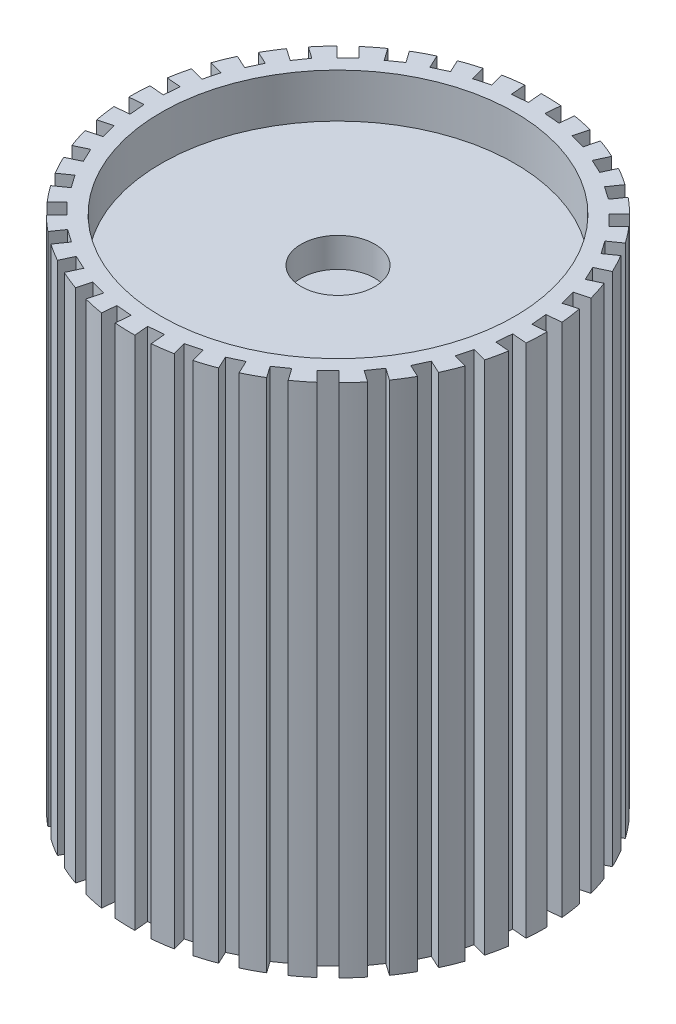
SolidWorks part; units mm, degrees
ref_plane "Front Plane" through (0, 0, 0) normal (0, 0, 1) x (1, 0, 0)
ref_plane "Top Plane" through (0, 0, 0) normal (0, 1, 0) x (1, 0, 0)
ref_plane "Right Plane" through (0, 0, 0) normal (1, 0, 0) x (0, 0, -1)
other "Configuration Table"
sketch "草图1" plane through (0, 0, 0) normal (0, 1, 0) x (1, 0, 0)
  circle A0 centre (0, 0) radius 13
  dimension "D1" = 26
extrude "凸台-拉伸1" add sketch "草图1" along normal blind 35
sketch "草图6" plane through (0, 35, 0) normal (0, 1, 0) x (1, 0, 0)
  circle A0 centre (0, 0) radius 14
  dimension "D1" = 28
extrude "凸台-拉伸4" add sketch "草图6" against normal through all
sketch "草图2" plane through (0, 35, 0) normal (0, 1, 0) x (1, 0, 0)
  circle A0 centre (0, 0) radius 12
  dimension "D1" = 24
extrude "切除-拉伸1" cut sketch "草图2" against normal blind 3
sketch "草图7" plane through (0, 35, 0) normal (0, 1, 0) x (1, 0, 0)
  line L0 (-15.6468, 4.1422) -> (-12.5671, 3.3269)
  line L1 (-15.6468, 4.1422) -> (-15.3762, 5.1646)
  line L2 (-12.5671, 3.3269) -> (-12.2964, 4.3493)
  line L3 (-15.3762, 5.1646) -> (-12.2964, 4.3493)
  line L4 (-14.6898, 6.7963) -> (-11.7985, 5.4586)
  line L5 (-14.6898, 6.7963) -> (-14.2457, 7.7562)
  line L6 (-14.2457, 7.7562) -> (-11.3544, 6.4185)
  line L7 (-11.7985, 5.4586) -> (-11.3544, 6.4185)
  line L8 (-13.2865, 9.2439) -> (-10.6713, 7.4245)
  line L9 (-13.2865, 9.2439) -> (-12.6825, 10.1121)
  line L10 (-12.6825, 10.1121) -> (-10.0673, 8.2926)
  line L11 (-10.6713, 7.4245) -> (-10.0673, 8.2926)
  line L12 (-11.4794, 11.4107) -> (-9.22, 9.1647)
  line L13 (-11.4794, 11.4107) -> (-10.7338, 12.1608)
  line L14 (-10.7338, 12.1608) -> (-8.4744, 9.9148)
  line L15 (-9.22, 9.1647) -> (-8.4744, 9.9148)
  line L16 (-9.3236, 13.2307) -> (-7.4884, 10.6265)
  line L17 (-9.3236, 13.2307) -> (-8.4591, 13.8399)
  line L18 (-8.4591, 13.8399) -> (-6.6239, 11.2358)
  line L19 (-7.4884, 10.6265) -> (-6.6239, 11.2358)
  line L20 (-6.8845, 14.6487) -> (-5.5294, 11.7654)
  line L21 (-6.8845, 14.6487) -> (-5.9273, 15.0986)
  line L22 (-5.9273, 15.0986) -> (-4.5722, 12.2153)
  line L23 (-5.5294, 11.7654) -> (-4.5722, 12.2153)
  line L24 (-4.2361, 15.6217) -> (-3.4024, 12.5469)
  line L25 (-4.2361, 15.6217) -> (-3.2154, 15.8985)
  line L26 (-3.2154, 15.8985) -> (-2.3816, 12.8237)
  line L27 (-3.4024, 12.5469) -> (-2.3816, 12.8237)
  line L28 (-1.4591, 16.1199) -> (-1.1719, 12.9471)
  line L29 (-1.4591, 16.1199) -> (-0.4058, 16.2153)
  line L30 (-0.4058, 16.2153) -> (-0.1186, 13.0424)
  line L31 (-1.1719, 12.9471) -> (-0.1186, 13.0424)
  line L32 (1.3622, 16.1284) -> (1.0941, 12.9539)
  line L33 (1.3622, 16.1284) -> (2.4161, 16.0394)
  line L34 (2.4161, 16.0394) -> (2.148, 12.8649)
  line L35 (1.0941, 12.9539) -> (2.148, 12.8649)
  line L36 (4.1422, 15.6468) -> (3.3269, 12.5671)
  line L37 (4.1422, 15.6468) -> (5.1646, 15.3762)
  line L38 (5.1646, 15.3762) -> (4.3493, 12.2964)
  line L39 (3.3269, 12.5671) -> (4.3493, 12.2964)
  line L40 (6.7963, 14.6898) -> (5.4586, 11.7985)
  line L41 (6.7963, 14.6898) -> (7.7562, 14.2457)
  line L42 (7.7562, 14.2457) -> (6.4185, 11.3544)
  line L43 (5.4586, 11.7985) -> (6.4185, 11.3544)
  line L44 (9.2439, 13.2865) -> (7.4245, 10.6713)
  line L45 (9.2439, 13.2865) -> (10.1121, 12.6825)
  line L46 (10.1121, 12.6825) -> (8.2926, 10.0673)
  line L47 (7.4245, 10.6713) -> (8.2926, 10.0673)
  line L48 (11.4107, 11.4794) -> (9.1647, 9.22)
  line L49 (11.4107, 11.4794) -> (12.1608, 10.7338)
  line L50 (12.1608, 10.7338) -> (9.9148, 8.4744)
  line L51 (9.1647, 9.22) -> (9.9148, 8.4744)
  line L52 (13.2307, 9.3236) -> (10.6265, 7.4884)
  line L53 (13.2307, 9.3236) -> (13.8399, 8.4591)
  line L54 (13.8399, 8.4591) -> (11.2358, 6.6239)
  line L55 (10.6265, 7.4884) -> (11.2358, 6.6239)
  line L56 (14.6487, 6.8845) -> (11.7654, 5.5294)
  line L57 (14.6487, 6.8845) -> (15.0986, 5.9273)
  line L58 (15.0986, 5.9273) -> (12.2153, 4.5722)
  line L59 (11.7654, 5.5294) -> (12.2153, 4.5722)
  line L60 (15.6217, 4.2361) -> (12.5469, 3.4024)
  line L61 (15.6217, 4.2361) -> (15.8985, 3.2154)
  line L62 (15.8985, 3.2154) -> (12.8237, 2.3816)
  line L63 (12.5469, 3.4024) -> (12.8237, 2.3816)
  line L64 (16.1199, 1.4591) -> (12.9471, 1.1719)
  line L65 (16.1199, 1.4591) -> (16.2153, 0.4058)
  line L66 (16.2153, 0.4058) -> (13.0424, 0.1186)
  line L67 (12.9471, 1.1719) -> (13.0424, 0.1186)
  line L68 (16.1284, -1.3622) -> (12.9539, -1.0941)
  line L69 (16.1284, -1.3622) -> (16.0394, -2.4161)
  line L70 (16.0394, -2.4161) -> (12.8649, -2.148)
  line L71 (12.9539, -1.0941) -> (12.8649, -2.148)
  line L72 (15.6468, -4.1422) -> (12.5671, -3.3269)
  line L73 (15.6468, -4.1422) -> (15.3762, -5.1646)
  line L74 (15.3762, -5.1646) -> (12.2964, -4.3493)
  line L75 (12.5671, -3.3269) -> (12.2964, -4.3493)
  line L76 (14.6898, -6.7963) -> (11.7985, -5.4586)
  line L77 (14.6898, -6.7963) -> (14.2457, -7.7562)
  line L78 (14.2457, -7.7562) -> (11.3544, -6.4185)
  line L79 (11.7985, -5.4586) -> (11.3544, -6.4185)
  line L80 (13.2865, -9.2439) -> (10.6713, -7.4245)
  line L81 (13.2865, -9.2439) -> (12.6825, -10.1121)
  line L82 (12.6825, -10.1121) -> (10.0673, -8.2926)
  line L83 (10.6713, -7.4245) -> (10.0673, -8.2926)
  line L84 (11.4794, -11.4107) -> (9.22, -9.1647)
  line L85 (11.4794, -11.4107) -> (10.7338, -12.1608)
  line L86 (10.7338, -12.1608) -> (8.4744, -9.9148)
  line L87 (9.22, -9.1647) -> (8.4744, -9.9148)
  line L88 (9.3236, -13.2307) -> (7.4884, -10.6265)
  line L89 (9.3236, -13.2307) -> (8.4591, -13.8399)
  line L90 (8.4591, -13.8399) -> (6.6239, -11.2358)
  line L91 (7.4884, -10.6265) -> (6.6239, -11.2358)
  line L92 (6.8845, -14.6487) -> (5.5294, -11.7654)
  line L93 (6.8845, -14.6487) -> (5.9273, -15.0986)
  line L94 (5.9273, -15.0986) -> (4.5722, -12.2153)
  line L95 (5.5294, -11.7654) -> (4.5722, -12.2153)
  line L96 (4.2361, -15.6217) -> (3.4024, -12.5469)
  line L97 (4.2361, -15.6217) -> (3.2154, -15.8985)
  line L98 (3.2154, -15.8985) -> (2.3816, -12.8237)
  line L99 (3.4024, -12.5469) -> (2.3816, -12.8237)
  line L100 (1.4591, -16.1199) -> (1.1719, -12.9471)
  line L101 (1.4591, -16.1199) -> (0.4058, -16.2153)
  line L102 (0.4058, -16.2153) -> (0.1186, -13.0424)
  line L103 (1.1719, -12.9471) -> (0.1186, -13.0424)
  line L104 (-1.3622, -16.1284) -> (-1.0941, -12.9539)
  line L105 (-1.3622, -16.1284) -> (-2.4161, -16.0394)
  line L106 (-2.4161, -16.0394) -> (-2.148, -12.8649)
  line L107 (-1.0941, -12.9539) -> (-2.148, -12.8649)
  line L108 (-4.1422, -15.6468) -> (-3.3269, -12.5671)
  line L109 (-4.1422, -15.6468) -> (-5.1646, -15.3762)
  line L110 (-5.1646, -15.3762) -> (-4.3493, -12.2964)
  line L111 (-3.3269, -12.5671) -> (-4.3493, -12.2964)
  line L112 (-6.7963, -14.6898) -> (-5.4586, -11.7985)
  line L113 (-6.7963, -14.6898) -> (-7.7562, -14.2457)
  line L114 (-7.7562, -14.2457) -> (-6.4185, -11.3544)
  line L115 (-5.4586, -11.7985) -> (-6.4185, -11.3544)
  line L116 (-9.2439, -13.2865) -> (-7.4245, -10.6713)
  line L117 (-9.2439, -13.2865) -> (-10.1121, -12.6825)
  line L118 (-10.1121, -12.6825) -> (-8.2926, -10.0673)
  line L119 (-7.4245, -10.6713) -> (-8.2926, -10.0673)
  line L120 (-11.4107, -11.4794) -> (-9.1647, -9.22)
  line L121 (-11.4107, -11.4794) -> (-12.1608, -10.7338)
  line L122 (-12.1608, -10.7338) -> (-9.9148, -8.4744)
  line L123 (-9.1647, -9.22) -> (-9.9148, -8.4744)
  line L124 (-13.2307, -9.3236) -> (-10.6265, -7.4884)
  line L125 (-13.2307, -9.3236) -> (-13.8399, -8.4591)
  line L126 (-13.8399, -8.4591) -> (-11.2358, -6.6239)
  line L127 (-10.6265, -7.4884) -> (-11.2358, -6.6239)
  line L128 (-14.6487, -6.8845) -> (-11.7654, -5.5294)
  line L129 (-14.6487, -6.8845) -> (-15.0986, -5.9273)
  line L130 (-15.0986, -5.9273) -> (-12.2153, -4.5722)
  line L131 (-11.7654, -5.5294) -> (-12.2153, -4.5722)
  line L132 (-15.6217, -4.2361) -> (-12.5469, -3.4024)
  line L133 (-15.6217, -4.2361) -> (-15.8985, -3.2154)
  line L134 (-15.8985, -3.2154) -> (-12.8237, -2.3816)
  line L135 (-12.5469, -3.4024) -> (-12.8237, -2.3816)
  line L136 (-16.1199, -1.4591) -> (-12.9471, -1.1719)
  line L137 (-16.1199, -1.4591) -> (-16.2153, -0.4058)
  line L138 (-16.2153, -0.4058) -> (-13.0424, -0.1186)
  line L139 (-12.9471, -1.1719) -> (-13.0424, -0.1186)
  line L140 (-16.1284, 1.3622) -> (-12.9539, 1.0941)
  line L141 (-16.1284, 1.3622) -> (-16.0394, 2.4161)
  line L142 (-16.0394, 2.4161) -> (-12.8649, 2.148)
  line L143 (-12.9539, 1.0941) -> (-12.8649, 2.148)
  circle A0 centre (0, 0) radius 13 construction
  point P150 (0, 0)
  dimension "D1" = 26
  dimension "D2" = 36
extrude "切除-拉伸2" cut sketch "草图7" against normal through all
sketch "草图8" plane through (0, 32, 0) normal (0, 1, 0) x (1, 0, 0)
  circle A0 centre (0, 0) radius 2.5
  dimension "D1" = 5
extrude "切除-拉伸3" cut sketch "草图8" against normal blind 2
